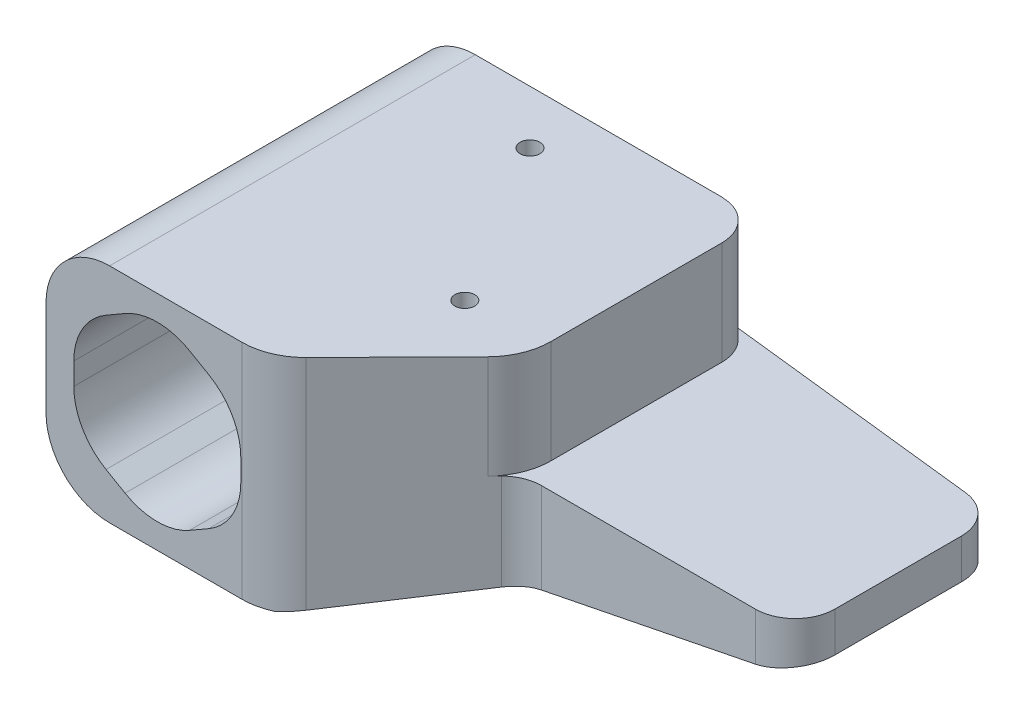
SolidWorks part; units mm, degrees
ref_plane "Front Plane" through (0, 0, 0) normal (0, 0, 1) x (1, 0, 0)
ref_plane "Top Plane" through (0, 0, 0) normal (0, 1, 0) x (1, 0, 0)
ref_plane "Right Plane" through (0, 0, 0) normal (1, 0, 0) x (0, 0, -1)
sketch "Sketch1" plane through (0, 0, 0) normal (0, 0, 1) x (1, 0, 0)
  line L1 (-14, -14) -> (14, -14)
  line L2 (-14, -14) -> (-14, 14)
  line L3 (-14, 14) -> (14, 14)
  line L4 (14, -14) -> (14, 14) construction
  line L5 (-14, -14) -> (14, 14) construction
  line L6 (-14, 14) -> (14, -14) construction
  line L7 (14, 14) -> (64, 14)
  line L8 (14, 14) -> (14, -14) construction
  line L9 (14, -14) -> (64, -14)
  line L10 (64, 14) -> (64, -14)
  line L11 (-10.5, 1.3856) -> (-10.5, -1.3856)
  line L12 (-6.45, -8.4004) -> (-4.05, -9.7861)
  line L13 (4.05, -9.7861) -> (6.45, -8.4004)
  line L14 (10.5, -1.3856) -> (10.5, 1.3856)
  line L15 (6.45, 8.4004) -> (4.05, 9.7861)
  line L16 (-4.05, 9.7861) -> (-6.45, 8.4004)
  circle A0 centre (0, 0) radius 10.5 construction
  circle A1 centre (0, 0) radius 10.5 construction
  arc A2 (-10.5, -1.3856) -> (-6.45, -8.4004) centre (-2.4, -1.3856) ccw
  arc A3 (-4.05, -9.7861) -> (4.05, -9.7861) centre (0, -2.7713) ccw
  arc A4 (6.45, -8.4004) -> (10.5, -1.3856) centre (2.4, -1.3856) ccw
  arc A5 (10.5, 1.3856) -> (6.45, 8.4004) centre (2.4, 1.3856) ccw
  arc A6 (4.05, 9.7861) -> (-4.05, 9.7861) centre (0, 2.7713) ccw
  arc A7 (-10.5, 1.3856) -> (-6.45, 8.4004) centre (-2.4, 1.3856) cw
  dimension "D1" = 21
  dimension "D4" = 8.1
  dimension "D2" = 50
  dimension "D3" = 28
extrude "Boss-Extrude1" add sketch "Sketch1" along normal mid plane 46 contours L10 L7 L3 L2 L1 L9 A0 region at (29.9466, 0, 0)
sketch "Sketch4" plane through (0, 14, 0) normal (0, 1, 0) x (1, 0, 0)
  line L0 (-14, -23) -> (64, -23) construction
  line L1 (4, 23) -> (4, -23) construction
  line L2 (7.6, 7) -> (64, 7) construction
  line L3 (-14, 23) -> (64, 23) construction
  line L5 (-14, -23) -> (-14, 23) construction
  line L6 (64, -23) -> (64, 23) construction
  circle A0 centre (20.1, -4.425) radius 1.25
  circle A1 centre (7.6, 16.275) radius 1.25
  circle A2 centre (7.6, 16.275) radius 9.275 construction
  dimension "D2" = 2.5
  dimension "D5" = 12.5
  dimension "D6" = 20.7
  dimension "D1" = 18.55
  dimension "D3" = 18
  dimension "D4" = 16.1
  dimension "D7" = 16
extrude "Cut-Extrude3" cut sketch "Sketch4" against normal blind 41
other "DeleteFace1" face at (6.3536, -8.4557, -16.3422) and patch yes
sketch "Sketch5" plane through (0, 0, 23) normal (0, 0, 1) x (1, 0, 0)
  line L0 (30, 14) -> (30, 1)
  line L1 (-14, 14) -> (64, 14) construction
  line L2 (30, 1) -> (64, 1)
  line L3 (64, 14) -> (64, -14) construction
  line L4 (64, -4) -> (14, -14)
  line L5 (-14, -14) -> (64, -14) construction
  line L6 (0, 0) -> (0, -14) construction
  line L7 (64, -4) -> (64, -14)
  line L8 (64, -14) -> (14, -14)
  line L9 (64, 1) -> (64, 14)
  line L10 (64, 14) -> (30, 14)
  dimension "D1" = 13
  dimension "D2" = 30
  dimension "D3" = 5
extrude "Cut-Extrude4" cut sketch "Sketch5" against normal through all
fillet "Fillet3" radius 5 1 edges at (30, 7.5, -23)
sketch "Sketch6" plane through (0, 14, 0) normal (0, 1, 0) x (1, 0, 0)
  line L0 (7.6, 16.275) -> (20.1, 16.275) construction
  line L1 (20.1, 16.275) -> (20.1, -4.425) construction
  line L2 (20.1, 5.925) -> (64, 5.925) construction
  line L3 (64, 23) -> (64, -23) construction
  line L5 (-14, -23) -> (30, -23) construction
  line L6 (64, -6.775) -> (64, -23)
  line L7 (64, -23) -> (14, -23)
  line L8 (64, -6.775) -> (30, -6.775)
  line L9 (30, 18) -> (30, -23) construction
  line L10 (30, -6.775) -> (14, -23)
  line L11 (25, 23) -> (64, 18.625)
  line L12 (64, 18.625) -> (64, 23)
  line L13 (64, 23) -> (25, 23)
  arc A0 (30, 18) -> (25, 23) centre (25, 18) ccw construction
  arc A1 (30, 18) -> (25, 23) centre (25, 18) ccw construction
  point P22 (0, 0)
  point P25 (25, 23)
  dimension "D1" = 25.4
extrude "Cut-Extrude5" cut sketch "Sketch6" against normal blind 39
fillet "Fillet4" radius 8 4 edges at (14, 0, 23) (30, 7.5, 6.775) (-14, -14, 0) (-14, 14, 0)
fillet "Fillet5" radius 5 3 edges at (30, -4.9, 6.775) (64, -1.5, -18.625) (64, -1.5, 6.775)
